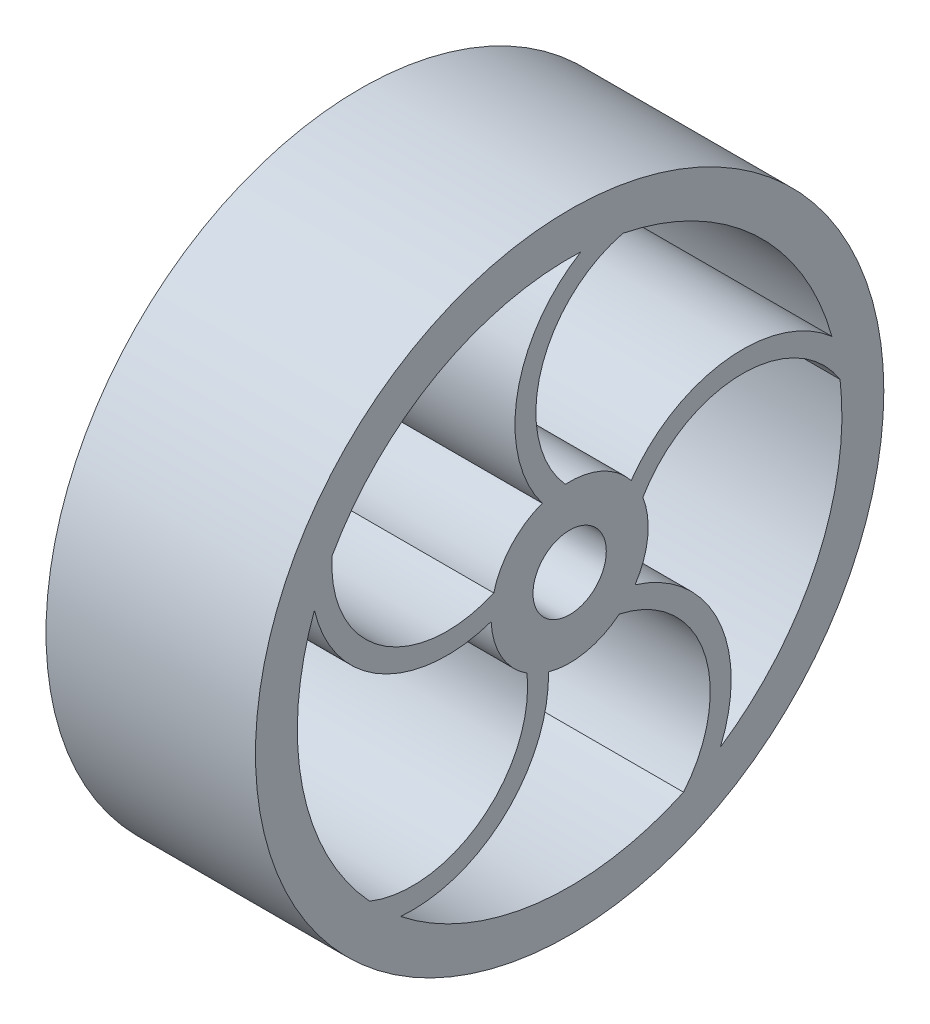
SolidWorks part; units mm, degrees
ref_plane "Front Plane" through (0, 0, 0) normal (0, 0, 1) x (1, 0, 0)
ref_plane "Top Plane" through (0, 0, 0) normal (0, 1, 0) x (1, 0, 0)
ref_plane "Right Plane" through (0, 0, 0) normal (1, 0, 0) x (0, 0, -1)
ref_plane "SIDE" through (0, 0, 0) normal (1, 0, 0) x (0, 0, -1)
ref_plane "SIDE END" through (-10, 0, 0) normal (1, 0, 0) x (0, 0, -1)
sketch "Sketch1" plane through (0, 0, 0) normal (1, 0, 0) x (0, 0, -1)
  circle A0 centre (0, 0) radius 1.75
  circle A1 centre (0, 0) radius 3.75
  dimension "D1" = 3.5
  dimension "D2" = 2
extrude "Boss-Extrude1" add sketch "Sketch1" against normal up to surface (10 mm away) up to plane "SIDE END"
ref_axis "rotation" through (-10, 0, 0) along (1, 0, 0)
sketch "Sketch2" plane through (0, 0, 0) normal (1, 0, 0) x (0, 0, -1)
  circle A0 centre (0, 0) radius 15
  circle A1 centre (0, 0) radius 13
  dimension "D2" = 30
  dimension "D1" = 2
extrude "Boss-Extrude2" add sketch "Sketch2" against normal up to surface (10 mm away) separate body up to plane "SIDE END"
sketch "Sketch3" plane through (0, 0, 0) normal (1, 0, 0) x (0, 0, -1)
  line L0 (0, 13) -> (0, 8.375) construction
  line L1 (0, 5.5) -> (0, -5.5) construction
  line L2 (0, 8.375) -> (0, 3.75) construction
  line L3 (0, 0) -> (-3.3302, 0) construction
  line L4 (-3.3302, 0) -> (-3.75, 0) construction
  line L5 (-3.75, 0) -> (-15, 0) construction
  circle A0 centre (0, 0) radius 8.375 construction
  arc A3 (-12.1859, 4.528) -> (-3.7466, -0.1588) centre (-5.8526, 5.9906) ccw
  circle A4 centre (0, 0) radius 15 construction
  arc A5 (-11.3405, 6.3556) -> (-3.6245, 0.9622) centre (-5.8526, 5.9906) ccw
  arc A6 (0.246, 3.7419) -> (0, 3.75) centre (0, 0) ccw construction
  arc A7 (-11.3405, 6.3556) -> (-12.1859, 4.528) centre (0, 0) ccw
  arc A8 (-4.2428, 12.2881) -> (-12.1859, 4.528) centre (-5.8526, 5.9906) ccw construction
  arc A9 (-6.0896, 11.4855) -> (-11.3405, 6.3556) centre (-5.8526, 5.9906) ccw construction
  arc A10 (-0.8746, 8.3292) -> (-6.0896, 11.4855) centre (-5.8526, 5.9906) ccw construction
  arc A11 (0, 8.8185) -> (-4.2428, 12.2881) centre (-5.8526, 5.9906) ccw construction
  arc A12 (0.246, 3.7419) -> (0.1952, 8.3727) centre (-5.8526, 5.9906) ccw construction
  arc A13 (0.1952, 8.3727) -> (0, 8.8185) centre (-5.8526, 5.9906) ccw construction
  arc A14 (-0.8774, 3.6459) -> (-0.8746, 8.3292) centre (-5.8526, 5.9906) ccw construction
  arc A15 (-3.6245, 0.9622) -> (-0.8774, 3.6459) centre (-5.8526, 5.9906) ccw construction
  arc A16 (-3.3302, 0) -> (0.246, 3.7419) centre (-5.8526, 5.9906) ccw construction
  arc A17 (-3.7466, -0.1588) -> (0.246, 3.7419) centre (0, 0) ccw construction
  arc A18 (-0.8774, 3.6459) -> (-3.6245, 0.9622) centre (0, 0) ccw construction
  arc A19 (-3.6245, 0.9622) -> (-3.7466, -0.1588) centre (0, 0) ccw
  arc A20 (-3.7466, -0.1588) -> (-3.3302, 0) centre (-5.8526, 5.9906) ccw construction
  arc A21 (-6.0896, 11.4855) -> (-11.3405, 6.3556) centre (0, 0) ccw construction
  arc A22 (-12.1859, 4.528) -> (-13, 0) centre (0, 0) ccw construction
  arc A23 (-4.2428, 12.2881) -> (-6.0896, 11.4855) centre (0, 0) ccw construction
  arc A24 (-13, 0) -> (0, 13) centre (0, 0) ccw construction
  arc A25 (0, 3.75) -> (-0.8774, 3.6459) centre (0, 0) ccw construction
  arc A26 (0, 13) -> (-4.2428, 12.2881) centre (0, 0) ccw construction
  point P7 (-31.5191, 6.5339)
  point P15 (-8.375, 0)
  point P30 (-60.3042, 19.6018)
  point P32 (-39.2588, 5.9782)
  dimension "D1" = 13
  dimension "D3" = 26
  dimension "D4" = 7.5
extrude "Boss-Extrude3" add sketch "Sketch3" against normal up to surface (10 mm away) up to plane "SIDE END"
pattern_circular "CirPattern1" count 5 over 360 about axis through (-10, 0, 0) along (1, 0, 0) of "Boss-Extrude3"
equation "\"wheelDia\"= 30"
equation "\"rodRia\"= 3.5"
equation "\"wheelThick\"= 2"
equation "\"spokeThick\"= 1"
equation "\"outWidth\"= 10"
equation "\"inWidth\"= 10"
equation "\"D1@Sketch1\"=\"rodRia\""
equation "\"D2@Sketch1\"=\"wheelThick\""
equation "\"D1@Sketch2\"=\"wheelThick\""
equation "\"D2@Sketch2\"=\"wheelDia\""
equation "\"D2@Sketch3\"=\"spokeThick\""
equation "\"D3@Sketch3\"=\"wheelDia\"- \"wheelThick\" - \"wheelThick\""
equation "\"D4@Sketch3\"=\"rodRia\"+\"wheelThick\"+\"wheelThick\""
